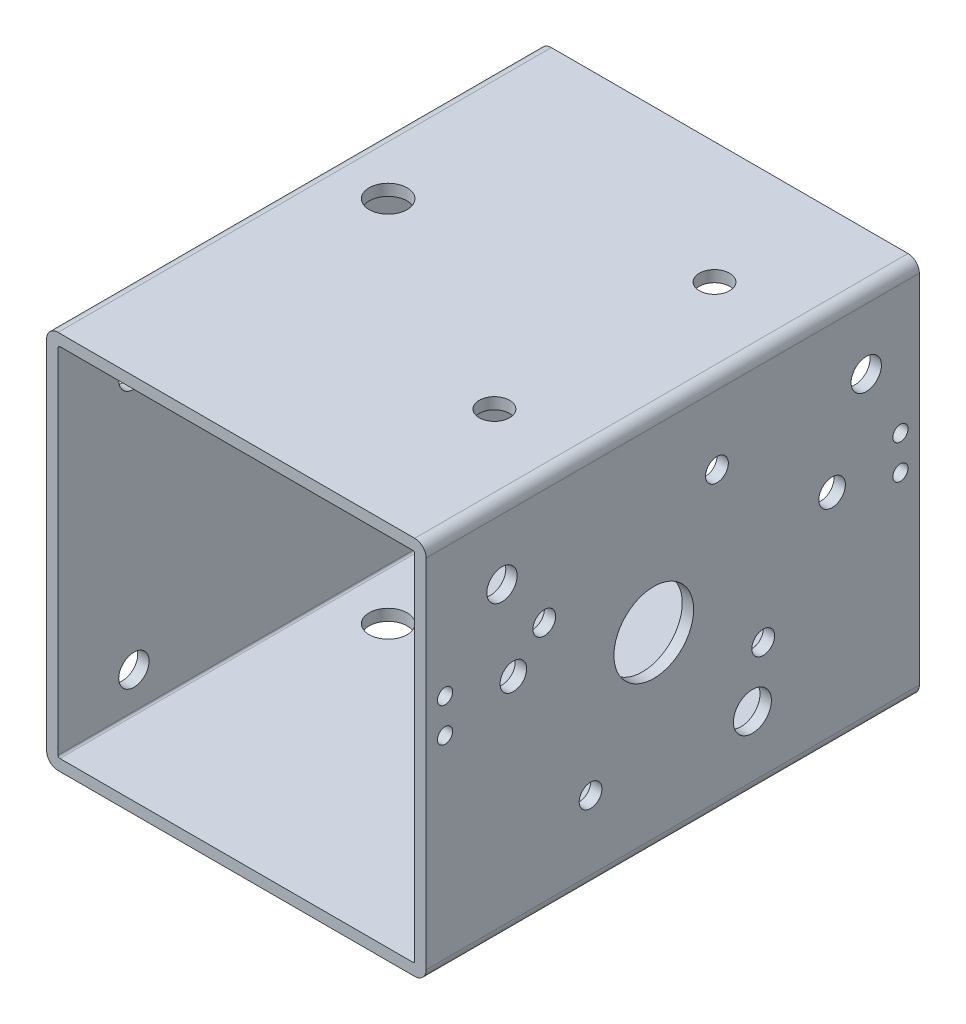
SolidWorks part; units mm, degrees
ref_plane "Front Plane" through (0, 0, 0) normal (0, 0, 1) x (1, 0, 0)
ref_plane "Top Plane" through (0, 0, 0) normal (0, 1, 0) x (1, 0, 0)
ref_plane "Right Plane" through (0, 0, 0) normal (1, 0, 0) x (0, 0, -1)
sketch "Sketch1" plane through (0, 0, 0) normal (0, 0, 1) x (1, 0, 0)
  line L1 (-50, 50) -> (50, 50)
  line L2 (-50, 50) -> (-50, -50)
  line L3 (-50, -50) -> (50, -50)
  line L4 (50, 50) -> (50, -50)
  line L5 (-50, 50) -> (50, -50) construction
  line L6 (-50, -50) -> (50, 50) construction
  point P0 (0, 0)
  dimension "D1" = 100
  dimension "D2" = 100
extrude "Extrude-Thin1" add sketch "Sketch1" along normal blind 130 thin thin type one direction reverse wall 3
fillet "Fillet1" radius 0.5 4 edges at (-47, -47, 65) (-47, 47, 65) (47, 47, 65) (47, -47, 65)
fillet "Fillet2" radius 3 4 edges at (50, -50, 65) (-50, -50, 65) (50, 50, 65) (-50, 50, 65)
sketch "Holes - top" plane through (0, 0, 0) normal (0, 1, 0) x (1, 0, 0)
  line L0 (-3, 0) -> (-3, -130) construction
  line L1 (47, -130) -> (-47, -130) construction
  line L2 (-23, 0) -> (-23, -130) construction
  line L3 (47, 0) -> (-47, 0) construction
  line L4 (17, 0) -> (17, -130) construction
  circle A0 centre (-34, -56) radius 11 construction
  circle A1 centre (28, -90) radius 11 construction
  circle A2 centre (28, -32) radius 11 construction
  dimension "D4" = 22
  dimension "D1" = 40
  dimension "D2" = 40
  dimension "D3" = 32
  dimension "D5" = 56
  dimension "D6" = 3
hole_wizard "Ø8.0 (8) Diameter Hole2" positions "Sketch6" profile "Sketch5" hole size "Ø8.0" standard "ANSI Metric" end condition through all
sketch "Sketch6" plane through (0, 50, 0) normal (0, 1, 0) x (1, 0, 0)
  point P0 (28, -32)
  point P6 (28, -90)
sketch "Sketch5" plane through (28, 50, 32) normal (1, 0, 0) x (0, 0, 1)
  line L0 (0, 0) -> (0, 100)
  line L1 (0, 100) -> (4, 100)
  line L2 (4, 100) -> (4, 0)
  line L5 (4, 0) -> (0, 0)
  line L11 (0, -6.35) -> (0, 107.95) construction
  dimension "Thru Hole Dia." = 8
  dimension "Thru Hole Depth" = 100
sketch "Holes - side" plane through (0, 0, 0) normal (1, 0, 0) x (0, 0, -1)
  line L0 (0, 0) -> (-130, 0) construction
  line L1 (-130, -47) -> (-130, 47) construction
  line L2 (-130, 20) -> (0, 20) construction
  line L3 (0, -47) -> (0, 47) construction
  line L4 (-130, -20) -> (0, -20) construction
  circle A0 centre (-110, 31) radius 11 construction
  circle A1 centre (-14, 31) radius 11 construction
  circle A2 centre (-44, -31) radius 11 construction
  dimension "D1" = 40
  dimension "D2" = 22
  dimension "D3" = 20
  dimension "D4" = 14
  dimension "D5" = 44
hole_wizard "Ø8.0 (8) Diameter Hole3" positions "Sketch9" profile "Sketch8" hole size "Ø8.0" standard "ANSI Metric" end condition through all
sketch "Sketch9" plane through (50, 0, 0) normal (1, 0, 0) x (0, 0, -1)
  point P0 (-14, 31)
  point P3 (-110, 31)
sketch "Sketch8" plane through (50, 31, 14) normal (0, 1, 0) x (0, 0, -1)
  line L0 (0, 0) -> (0, 100)
  line L1 (0, 100) -> (4, 100)
  line L2 (4, 100) -> (4, 0)
  line L5 (4, 0) -> (0, 0)
  line L11 (0, -6.35) -> (0, 107.95) construction
  dimension "Thru Hole Dia." = 8
  dimension "Thru Hole Depth" = 100
hole_wizard "Ø10.0 (10) Diameter Hole1" positions "Sketch12" profile "Sketch11" hole size "Ø10.0" standard "ANSI Metric" end condition through all
sketch "Sketch12" plane through (0, 50, 0) normal (0, 1, 0) x (1, 0, 0)
  point P0 (-34, -56)
sketch "Sketch11" plane through (-34, 50, 56) normal (1, 0, 0) x (0, 0, 1)
  line L0 (0, 0) -> (0, 100)
  line L1 (0, 100) -> (5, 100)
  line L2 (5, 100) -> (5, 0)
  line L5 (5, 0) -> (0, 0)
  line L11 (0, -6.35) -> (0, 107.95) construction
  dimension "Thru Hole Dia." = 10
  dimension "Thru Hole Depth" = 100
hole_wizard "Ø10.0 (10) Diameter Hole2" positions "Sketch14" profile "Sketch13" hole size "Ø10.0" standard "ANSI Metric" end condition through all
sketch "Sketch14" plane through (50, 0, 0) normal (1, 0, 0) x (0, 0, -1)
  point P0 (-44, -31)
sketch "Sketch13" plane through (50, -31, 44) normal (0, 1, 0) x (0, 0, -1)
  line L0 (0, 0) -> (0, 100)
  line L1 (0, 100) -> (5, 100)
  line L2 (5, 100) -> (5, 0)
  line L5 (5, 0) -> (0, 0)
  line L11 (0, -6.35) -> (0, 107.95) construction
  dimension "Thru Hole Dia." = 10
  dimension "Thru Hole Depth" = 100
hole_wizard "Ø6.0 (6) Diameter Hole2" positions "Sketch18" profile "Sketch17" hole size "Ø6.0" standard "ANSI Metric" end condition up to next
sketch "Sketch18" plane through (-50, 0, 0) normal (-1, 0, 0) x (0, 0, 1)
  line L0 (56, 35) -> (56, -15) construction
  point P0 (56, -15)
  point P2 (56, 35)
  dimension "D1" = 56
  dimension "D2" = 35
  dimension "D3" = 15
sketch "Sketch17" plane through (-50, -15, 56) normal (0, 1, 0) x (0, 0, 1)
  line L0 (0, 0) -> (0, 3)
  line L1 (0, 3) -> (3, 3)
  line L2 (3, 3) -> (3, 0)
  line L5 (3, 0) -> (0, 0)
  line L11 (0, -6.35) -> (0, 107.95) construction
  dimension "Thru Hole Dia." = 6
  dimension "Thru Hole Depth" = 3
hole_wizard "Ø6.0 (6) Diameter Hole3" positions "Sketch21" profile "Sketch20" hole size "Ø6.0" standard "ANSI Metric" end condition up to next
sketch "Sketch21" plane through (0, -50, 0) normal (0, -1, 0) x (-1, 0, 0)
  line L0 (20, -44) -> (-35, -44) construction
  point P0 (20, -44)
  point P2 (-35, -44)
  dimension "D1" = 44
  dimension "D2" = 35
  dimension "D3" = 20
sketch "Sketch20" plane through (-20, -50, 44) normal (1, 0, 0) x (0, 0, -1)
  line L0 (0, 0) -> (0, 3)
  line L1 (0, 3) -> (3, 3)
  line L2 (3, 3) -> (3, 0)
  line L5 (3, 0) -> (0, 0)
  line L11 (0, -6.35) -> (0, 107.95) construction
  dimension "Thru Hole Dia." = 6
  dimension "Thru Hole Depth" = 3
sketch "Holes - Nema 23 motor" plane through (0, 0, 0) normal (1, 0, 0) x (0, 0, -1)
  line L0 (-98.8427, 16.6524) -> (-53.3476, 28.8427) construction
  line L1 (-98.8427, 16.6524) -> (-86.6524, -28.8427) construction
  line L2 (-53.3476, 28.8427) -> (-41.1573, -16.6524) construction
  line L3 (-86.6524, -28.8427) -> (-41.1573, -16.6524) construction
  line L4 (-98.8427, 16.6524) -> (-41.1573, -16.6524) construction
  line L5 (-53.3476, 28.8427) -> (-86.6524, -28.8427) construction
  line L6 (0, 0) -> (-130, 0) construction
  point P1 (-70, 0)
  dimension "D1" = 70
  dimension "D2" = 47.1
  dimension "D3" = 47.1
  dimension "D4" = 15
hole_wizard "Ø21.0 (21) Diameter Hole1" positions "Sketch24" profile "Sketch23" hole size "Ø21.0" standard "ANSI Metric" end condition up to next
sketch "Sketch24" plane through (50, 0, 0) normal (1, 0, 0) x (0, 0, -1)
  point P0 (-70, 0)
sketch "Sketch23" plane through (50, 0, 70) normal (0, 1, 0) x (0, 0, -1)
  line L0 (0, 0) -> (0, 3)
  line L1 (0, 3) -> (10.5, 3)
  line L2 (10.5, 3) -> (10.5, 0)
  line L5 (10.5, 0) -> (0, 0)
  line L11 (0, -6.35) -> (0, 107.95) construction
  dimension "Thru Hole Dia." = 21
  dimension "Thru Hole Depth" = 3
hole_wizard "Ø6.0 (6) Diameter Hole1" positions "Sketch26" profile "Sketch25" hole size "Ø6.0" standard "ANSI Metric" end condition up to next
sketch "Sketch26" plane through (50, 0, 0) normal (1, 0, 0) x (0, 0, -1)
  point P0 (-41.1573, -16.6524)
  point P3 (-53.3476, 28.8427)
  point P6 (-98.8427, 16.6524)
  point P9 (-86.6524, -28.8427)
sketch "Sketch25" plane through (50, -16.6524, 41.1573) normal (0, 1, 0) x (0, 0, -1)
  line L0 (0, 0) -> (0, 3)
  line L1 (0, 3) -> (3, 3)
  line L2 (3, 3) -> (3, 0)
  line L5 (3, 0) -> (0, 0)
  line L11 (0, -6.35) -> (0, 107.95) construction
  dimension "Thru Hole Dia." = 6
  dimension "Thru Hole Depth" = 3
sketch "Sketch27" plane through (50, 0, 0) normal (1, 0, 0) x (0, 0, -1)
  line L1 (0, -47) -> (0, 47) construction
  line L2 (-130, 50) -> (0, 50) construction
  line L3 (-65, 66.9997) -> (-65, -40.3101) construction
  line L4 (-130, -47) -> (-130, 47) construction
  circle A0 centre (-5, 13) radius 2
  circle A1 centre (-5, 4) radius 2
  circle A2 centre (-23, 8.5) radius 3.5
  circle A3 centre (-107, 8.5) radius 3.5
  circle A4 centre (-125, 4) radius 2
  circle A5 centre (-125, 13) radius 2
  dimension "D1" = 4
  dimension "D2" = 9
  dimension "D3" = 5
  dimension "D4" = 46
  dimension "D7" = 18
  dimension "D8" = 4.5
  dimension "D9" = 7
  dimension "D5" = 0
  dimension "D6" = 65
extrude "Cut-Extrude1" cut sketch "Sketch27" against normal up to next
sketch "Sketch31" plane through (-50, 0, 0) normal (-1, 0, 0) x (0, 0, 1)
  line L0 (0, 47) -> (0, -47) construction
  line L1 (130, 47) -> (130, -47) construction
  line L2 (0, -47) -> (130, -47) construction
  circle A0 centre (14, -37) radius 4
  circle A1 centre (110, -37) radius 4
  dimension "D1" = 8
  dimension "D2" = 8
  dimension "D3" = 14
  dimension "D4" = 20
  dimension "D5" = 10
extrude "Cut-Extrude2" cut sketch "Sketch31" against normal up to next
equation "\"L\"= 130"
equation "\"D1@Extrude-Thin1\"=\"L\""
equation "\"d-bearing\"= 22'diameter of bearing"
equation "\"D4@Holes - top\"=\"d-bearing\""
equation "\"D2@Holes - side\"=\"d-bearing\""
